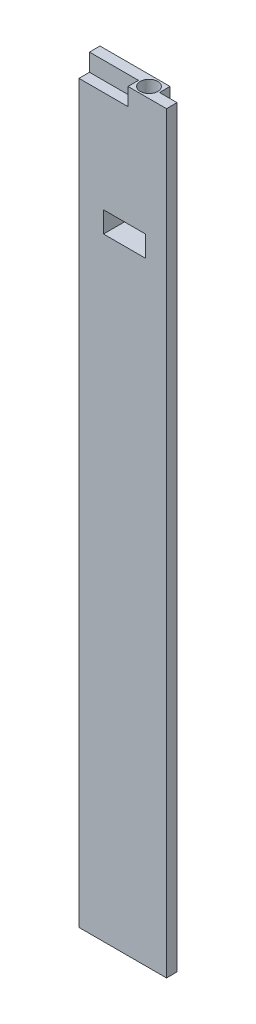
SolidWorks part; units mm, degrees
material "Plywood"
ref_plane "Plan de face" through (0, 0, 0) normal (0, 0, 1) x (1, 0, 0)
ref_plane "Plan de dessus" through (0, 0, 0) normal (0, 1, 0) x (1, 0, 0)
ref_plane "Plan de droite" through (0, 0, 0) normal (1, 0, 0) x (0, 0, -1)
sketch "Esquisse1" plane through (0, 0, 0) normal (0, 1, 0) x (1, 0, 0)
  line L0 (0, 0) -> (0, 6)
  line L1 (0, 6) -> (20, 6)
  line L2 (20, 6) -> (20, 3)
  line L3 (20, 3) -> (25, 3)
  line L4 (25, 3) -> (25, 0)
  line L5 (25, 0) -> (0, 0)
  dimension "D1" = 6
  dimension "D2" = 3
  dimension "D3" = 5
  dimension "D4" = 25
extrude "Boss.-Extru.1" add sketch "Esquisse1" along normal blind 215
sketch "Esquisse2" plane through (0, 215, 0) normal (0, 1, 0) x (1, 0, 0)
  line L1 (0, 0) -> (14, 0)
  line L2 (0, 0) -> (0, 3)
  line L3 (0, 3) -> (14, 3)
  line L4 (14, 0) -> (14, 3)
  dimension "D1" = 3
  dimension "D2" = 14
extrude "Enlèv. mat.-Extru.1" cut sketch "Esquisse2" against normal blind 5
sketch "Esquisse3" plane through (0, 0, 0) normal (0, 0, 1) x (1, 0, 0)
  line L0 (25, 175) -> (2, 175) construction
  line L1 (19, 175) -> (7, 175)
  line L2 (19, 175) -> (19, 181)
  line L3 (19, 181) -> (7, 181)
  line L4 (7, 175) -> (7, 181)
  line L5 (25, 215) -> (25, 0) construction
  dimension "D1" = 6
  dimension "D2" = 6
  dimension "D3" = 12
extrude "Enlèv. mat.-Extru.2" cut sketch "Esquisse3" against normal through all
sketch "Esquisse4" plane through (0, 215, 0) normal (0, 1, 0) x (1, 0, 0)
  line L0 (25, 3) -> (20, 3) construction
  line L1 (14, 0) -> (14, 3) construction
  circle A0 centre (17, 3) radius 2.5
  dimension "D2" = 5
  dimension "D1" = 3
extrude "Enlèv. mat.-Extru.3" cut sketch "Esquisse4" against normal blind 10
